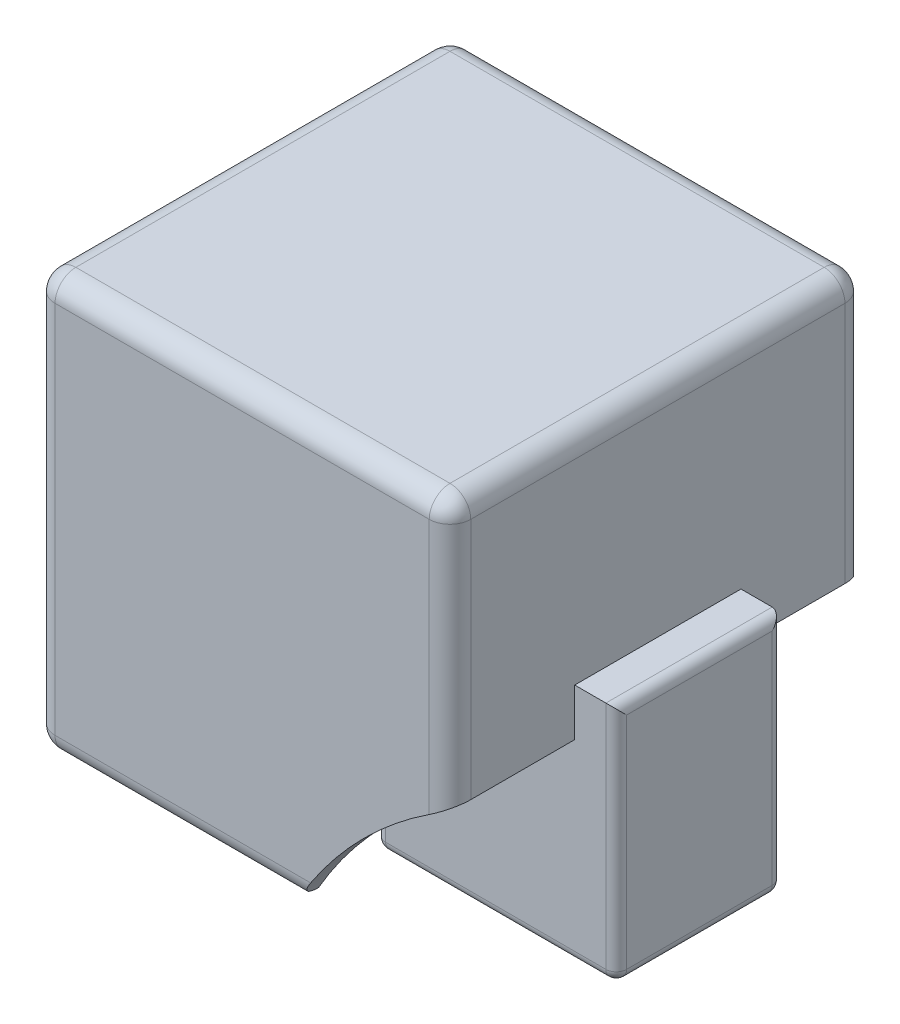
SolidWorks part; units mm, degrees
material "PS HI"
ref_plane "Ön Düzlem" through (0, 0, 0) normal (0, 0, 1) x (1, 0, 0)
ref_plane "Üst Düzlem" through (0, 0, 0) normal (0, 1, 0) x (1, 0, 0)
ref_plane "Sağ Düzlem" through (0, 0, 0) normal (1, 0, 0) x (0, 0, -1)
sketch "Çizim1" plane through (0, 0, 0) normal (0, 0, 1) x (1, 0, 0)
  line L1 (-10, -10) -> (10, -10)
  line L2 (-10, -10) -> (-10, 10)
  line L3 (-10, 10) -> (10, 10)
  line L4 (10, -10) -> (10, 10)
  line L5 (-10, -10) -> (10, 10) construction
  line L6 (-10, 10) -> (10, -10) construction
  point P0 (0, 0)
  dimension "D1" = 20
  dimension "D2" = 20
extrude "Yükseklik-Ekstrüzyon1" add sketch "Çizim1" along normal mid plane 20
shell "İç Boşaltma1" thickness 1 removed face at (0, -10, 0)
sketch "Çizim2" plane through (0, 0, 10) normal (0, 0, 1) x (1, 0, 0)
  circle A0 centre (20, -20) radius 20
extrude "Kes-Ekstrüzyon1" cut sketch "Çizim2" against normal blind 29
sketch "Çizim3" plane through (0, 0, 0) normal (0, 0, 1) x (1, 0, 0)
  line L0 (10, -2.1394) -> (12, -2.1394)
  line L1 (10, -2.6795) -> (10, 10) construction
  line L2 (2.1394, -11) -> (2.1394, -2.1394)
  line L3 (2.1394, -2.1394) -> (10, -2.1394)
  line L4 (2.1394, -11) -> (2.1394, -13)
  line L5 (2.1394, -13) -> (12, -13)
  line L6 (12, -13) -> (12, -2.1394)
  dimension "D1" = 2
  dimension "D2" = 2
extrude "Yükseklik-Ekstrüzyon2" add sketch "Çizim3" along normal mid plane 8
sketch "Çizim4" plane through (12, 0, 0) normal (1, 0, 0) x (0, 0, -1)
  line L0 (-4, -2.1394) -> (-4, -0.4041)
  line L1 (-4, -0.4041) -> (4, -0.4041)
  line L2 (4, -0.4041) -> (4, -2.1394)
  line L3 (4, -2.1394) -> (-4, -2.1394)
  arc A0 (9, -2.1394) -> (-9, -2.1394) centre (0, -20) ccw construction
extrude "Yükseklik-Ekstrüzyon3" add sketch "Çizim4" against normal up to body separate body
sketch "Çizim6" plane through (0, -13, 0) normal (0, -1, 0) x (1, 0, 0)
  line L0 (2.1394, -4) -> (0.4041, -4)
  line L1 (0.4041, -4) -> (0.4041, 4)
  line L2 (0.4041, 4) -> (2.1394, 4)
  line L3 (2.1394, 4) -> (2.1394, -4)
  arc A0 (2.1394, 9) -> (2.1394, -9) centre (20, 0) ccw construction
extrude "Yükseklik-Ekstrüzyon4" add sketch "Çizim6" against normal up to vertex (10.8606 mm away) up to point (2.1394, -2.1394, 4)
shell "İç Boşaltma2" thickness 1 removed face at (6.202, -13, 0)
sketch "Çizim7" plane through (0, -3.1394, 0) normal (0, -1, 0) x (1, 0, 0)
  line L0 (10, 3) -> (11, 3)
  line L1 (11, 3) -> (11, -3)
  line L2 (11, -3) -> (10, -3)
  line L3 (10, -3) -> (10, 3)
extrude "Yükseklik-Ekstrüzyon5" add sketch "Çizim7" against normal up to surface (1.7353 mm away) up to face at (10.5, -1.4041, 0)
fillet "Radyus1" radius 1 8 edges at (-10, 0, 10) (-10, 0, -10) (10, 3.6603, -10) (10, 3.6603, 10) (10, 10, 0) (0, 10, 10) (-10, 10, 0) (0, 10, -10)
fillet "Radyus2" radius 1 5 edges at (-3.1603, -10, 10) (-9.7071, -10, 9.7071) (-3.1603, -10, -10) (-9.7071, -10, -9.7071) (-10, -10, 0)
sketch "Çizim8" plane through (0, 0, 4) normal (0, 0, 1) x (1, 0, 0)
  line L0 (13.1602, -15) -> (13.1602, -12)
  line L1 (13.1602, -12) -> (0.4041, -12)
  line L2 (0.4041, -2.1394) -> (0.4041, -13) construction
  line L3 (0.4041, -12) -> (0.4041, -15)
  line L4 (0.4041, -15) -> (13.1602, -15)
  dimension "D1" = 3
extrude "Kes-Ekstrüzyon2" cut sketch "Çizim8" against normal blind 10
fillet "Radyus3" radius 0.5 9 edges at (0.4041, -7.0697, -4) (0.4041, -7.0697, 4) (0.4041, -12, 0) (6.202, -12, -4) (6.202, -12, 4) (12, -12, 0) (12, -6.202, -4) (12, -6.202, 4) (12, -0.4041, 0)
